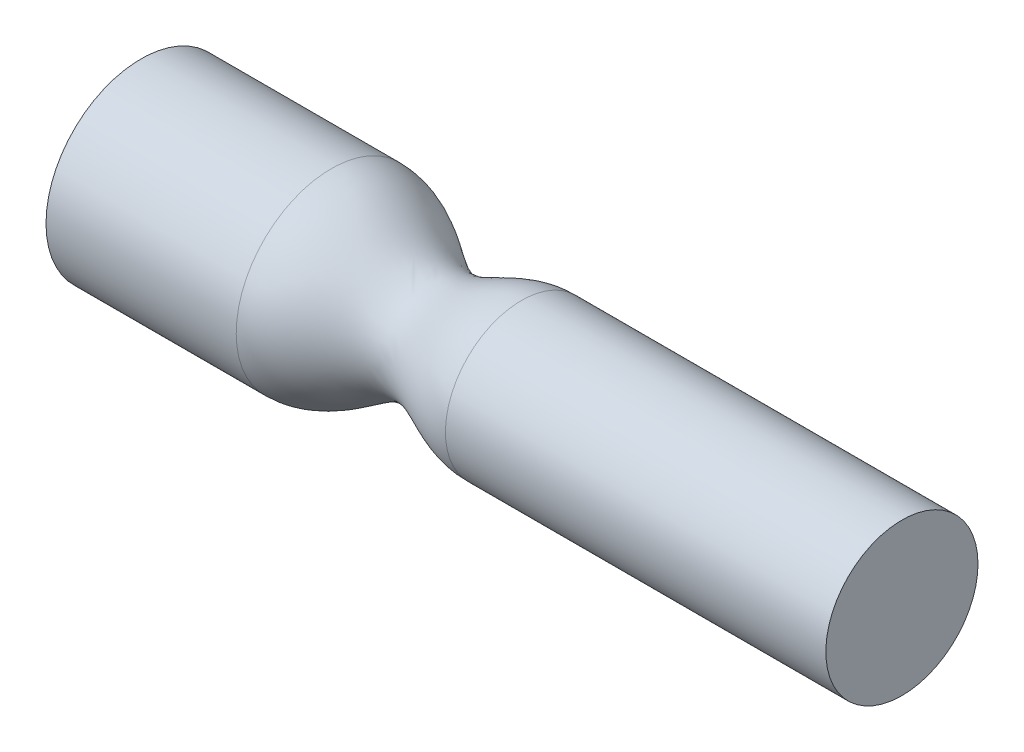
SolidWorks part; units mm, degrees
ref_plane "정면" through (0, 0, 0) normal (0, 0, 1) x (1, 0, 0)
ref_plane "윗면" through (0, 0, 0) normal (0, 1, 0) x (1, 0, 0)
ref_plane "우측면" through (0, 0, 0) normal (1, 0, 0) x (0, 0, -1)
sketch "Sketch1" plane through (0, 0, 0) normal (1, 0, 0) x (0, 0, -1)
  circle A0 centre (0, 0) radius 5
  dimension "D1" = 10
ref_plane "Plane1" through (10, 0, 0) normal (1, 0, 0) x (0, 0, -1)
sketch "Sketch2" plane through (10, 0, 0) normal (1, 0, 0) x (0, 0, -1)
  circle A0 centre (0, 0) radius 4
  dimension "D1" = 8
loft "Loft1" add profiles "Sketch2", "Sketch1" start constraint normal to profile start tangent length 1 end constraint normal to profile end tangent length 1 connector at (10, 1.1425, 3.8334) connector at (0, 4.3494, -2.4664)
extrude "Boss-Extrude1" add sketch "Sketch2<2>" along normal blind 20
sketch "Sketch2<2>" plane through (10, 0, 0) normal (1, 0, 0) x (0, 0, -1) same geometry as "Sketch2"
extrude "Boss-Extrude2" add sketch "Sketch1<2>" against normal blind 10
sketch "Sketch1<2>" plane through (0, 0, 0) normal (1, 0, 0) x (0, 0, -1) same geometry as "Sketch1"
